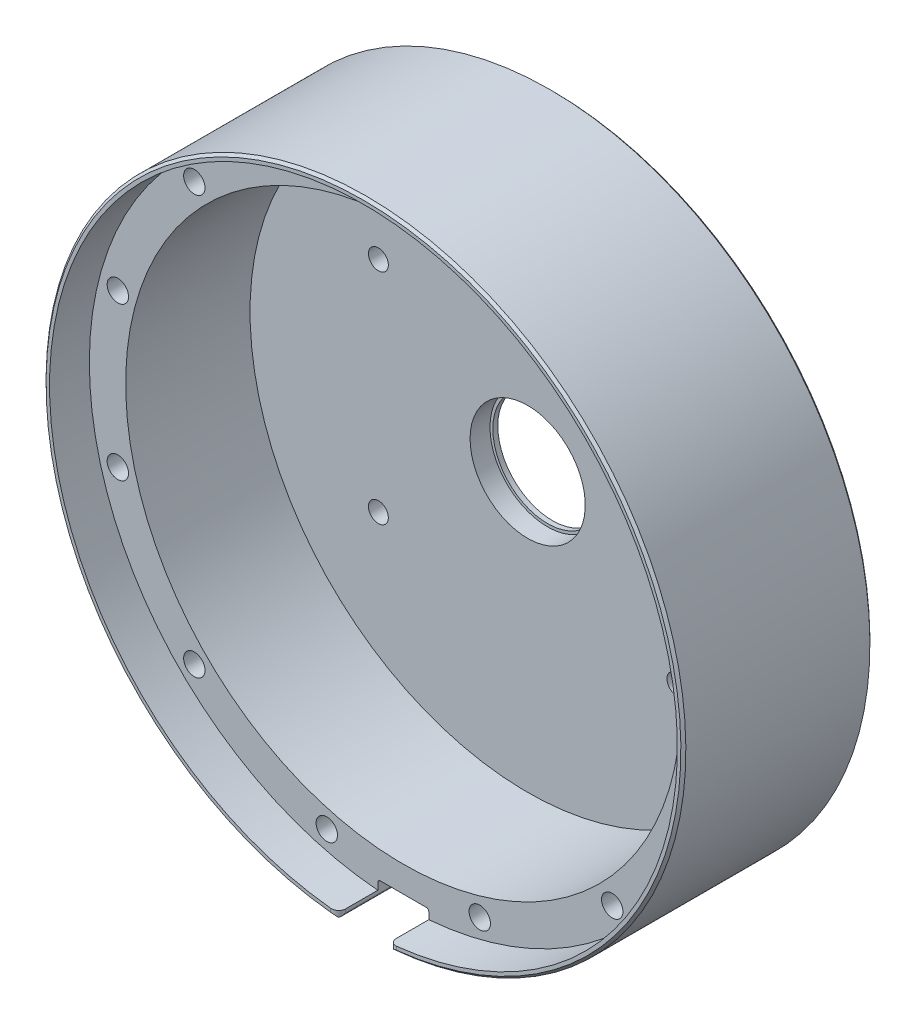
SolidWorks part; units mm, degrees
material "ABS"
ref_plane "Front Plane" through (0, 0, 0) normal (0, 0, 1) x (1, 0, 0)
ref_plane "Top Plane" through (0, 0, 0) normal (0, 1, 0) x (1, 0, 0)
ref_plane "Right Plane" through (0, 0, 0) normal (1, 0, 0) x (0, 0, -1)
sketch "Actuator Housing Mount" plane through (0, 0, 19) normal (0, 0, 1) x (1, 0, 0)
  line L0 (0, 0) -> (63, 0) construction
  line L1 (0, 0) -> (62.0607, 16.6291) construction
  circle A1 centre (57.376, 15.3739) radius 3.6 construction
  circle A2 centre (0, 0) radius 55.8
  circle A3 centre (57.376, 15.3739) radius 1.6
  circle A4 centre (57.376, -15.3739) radius 1.6
  circle A5 centre (42.0021, -42.0021) radius 1.6
  circle A6 centre (15.3739, -57.376) radius 1.6
  circle A7 centre (-15.3739, -57.376) radius 1.6
  circle A8 centre (-42.0021, -42.0021) radius 1.6
  circle A9 centre (-57.376, -15.3739) radius 1.6
  circle A10 centre (-57.376, 15.3739) radius 1.6
  circle A11 centre (-42.0021, 42.0021) radius 1.6
  circle A12 centre (-15.3739, 57.376) radius 1.6
  circle A13 centre (15.3739, 57.376) radius 1.6
  circle A14 centre (42.0021, 42.0021) radius 1.6
  circle A15 centre (0, 0) radius 64.3
  point P35 (0, 0)
extrude "Actuator Housing Wall" add sketch "Actuator Housing Mount" against normal blind 25
sketch "Sketch2" plane through (0, 0, -6) normal (0, 0, -1) x (-1, 0, 0)
  circle A0 centre (0, 0) radius 64.3
  circle A1 centre (0, 0) radius 64.3 construction
  circle M2 centre (-42.0021, 42.0021) radius 1.6
  circle M3 centre (-15.3739, 57.376) radius 1.6
  circle M4 centre (15.3739, 57.376) radius 1.6
  circle M5 centre (42.0021, 42.0021) radius 1.6
  circle M6 centre (57.376, 15.3739) radius 1.6
  circle M7 centre (57.376, -15.3739) radius 1.6
  circle M8 centre (42.0021, -42.0021) radius 1.6
  circle M9 centre (15.3739, -57.376) radius 1.6
  circle M10 centre (-15.3739, -57.376) radius 1.6
  circle M11 centre (-42.0021, -42.0021) radius 1.6
  circle M12 centre (0, 0) radius 55.8
  circle M13 centre (-57.376, -15.3739) radius 1.6
  circle M14 centre (-57.376, 15.3739) radius 1.6
  circle M15 centre (0, 0) radius 64.3
extrude "Boss-Extrude2" add sketch "Sketch2" along normal blind 5 contours M15 M3 M5 M7 M9 M11 M13 M14 M12 M10 M8 M6 M4 M2 | M12
sketch "Sketch3" plane through (0, 0, -11) normal (0, 0, -1) x (-1, 0, 0)
  circle A0 centre (0, 0) radius 11.575
  dimension "D1" = 23.15
extrude "Cut-Extrude1" cut sketch "Sketch3" along normal blind 4 from surface at -5 starting at face at (55.8, 0, -6)
sketch "Sketch4" plane through (0, 0, -11) normal (0, 0, -1) x (-1, 0, 0)
  circle A0 centre (0, 0) radius 11
  dimension "D1" = 22
extrude "Cut-Extrude2" cut sketch "Sketch4" against normal blind 4
sketch "Sketch6" plane through (0, 0, 19) normal (0, 0, 1) x (1, 0, 0)
  circle A0 centre (0, 0) radius 64.3
  circle A1 centre (0, 0) radius 63.1
  dimension "D1" = 128.6
  dimension "D2" = 126.2
extrude "Boss-Extrude3" add sketch "Sketch6" along normal blind 8
sketch "Sketch7" plane through (0, 0, 19) normal (0, 0, 1) x (1, 0, 0)
  circle A0 centre (57.376, -15.3739) radius 2.15
  circle A1 centre (42.0021, -42.0021) radius 2.15
  circle A2 centre (15.3739, -57.376) radius 2.15
  circle A3 centre (-15.3739, -57.376) radius 2.15
  circle A4 centre (-42.0021, -42.0021) radius 2.15
  circle A5 centre (-57.376, -15.3739) radius 2.15
  circle A6 centre (-57.376, 15.3739) radius 2.15
  circle A7 centre (-42.0021, 42.0021) radius 2.15
  circle A8 centre (-15.3739, 57.376) radius 2.15
  circle A9 centre (15.3739, 57.376) radius 2.15
  circle A10 centre (42.0021, 42.0021) radius 2.15
  circle A11 centre (57.376, 15.3739) radius 2.15
  point P27 (0, 0)
  dimension "D1" = 12
  dimension "M3 Insert" = 4.3
extrude "M3 Insert L12" cut sketch "Sketch7" against normal blind 12
chamfer "Chamfer2" distance 0.5 angle 45 2 edges at (64.3, 0, 27) (-64.3, 0, -11)
sketch "Sketch8" plane through (0, 0, 27) normal (0, 0, 1) x (1, 0, 0)
  line L1 (-5.1219, -61) -> (5.1219, -61)
  line L2 (-5.1219, -61) -> (-5.1219, -65.6855)
  line L3 (-5.1219, -65.6855) -> (5.1219, -65.6855)
  line L4 (5.1219, -61) -> (5.1219, -65.6855)
  dimension "D1" = 10.2438
extrude "Cut-Extrude4" cut sketch "Sketch8" against normal through all
fillet "Fillet2" radius 0.5 2 edges at (-5.1219, -64.0957, 8) (5.1219, -64.0957, 8)
fillet "Fillet3" radius 1.5 2 edges at (5.1219, -63.2218, 27) (-5.1219, -63.2218, 27)
fillet "Fillet5" radius 1.5 1 edges at (0, -61, -11)
fillet "Fillet6" radius 0.5 4 edges at (-5.1223, -63.5729, -11) (5.1223, -63.5729, -11) (-5.1219, -61.5259, -11) (5.1219, -61.5259, -11)
fillet "Fillet7" radius 0.5 6 edges at (-5.1219, -61, 4.75) (-5.1219, -60.9013, -10.0352) (5.1219, -61, 4.75) (5.1219, -60.9013, -10.0352) (-5.292, -60.0979, -10.8757) (5.292, -60.0979, -10.8757)
sketch "Sketch9" plane through (0, 0, -11) normal (0, 0, -1) x (-1, 0, 0)
  line L1 (-30, -22) -> (30, -22) construction
  line L2 (-30, -22) -> (-30, 22) construction
  line L3 (-30, 22) -> (30, 22) construction
  line L4 (30, -22) -> (30, 22) construction
  line L5 (-30, -22) -> (30, 22) construction
  line L6 (-30, 22) -> (30, -22) construction
  circle A0 centre (-30, 22) radius 2
  circle A1 centre (30, 22) radius 2
  circle A2 centre (30, -22) radius 2
  circle A3 centre (-30, -22) radius 2
  point P0 (0, 0)
  dimension "D3" = 4
  dimension "D1" = 60
  dimension "D2" = 44
extrude "Cut-Extrude5" cut sketch "Sketch9" against normal blind 10
